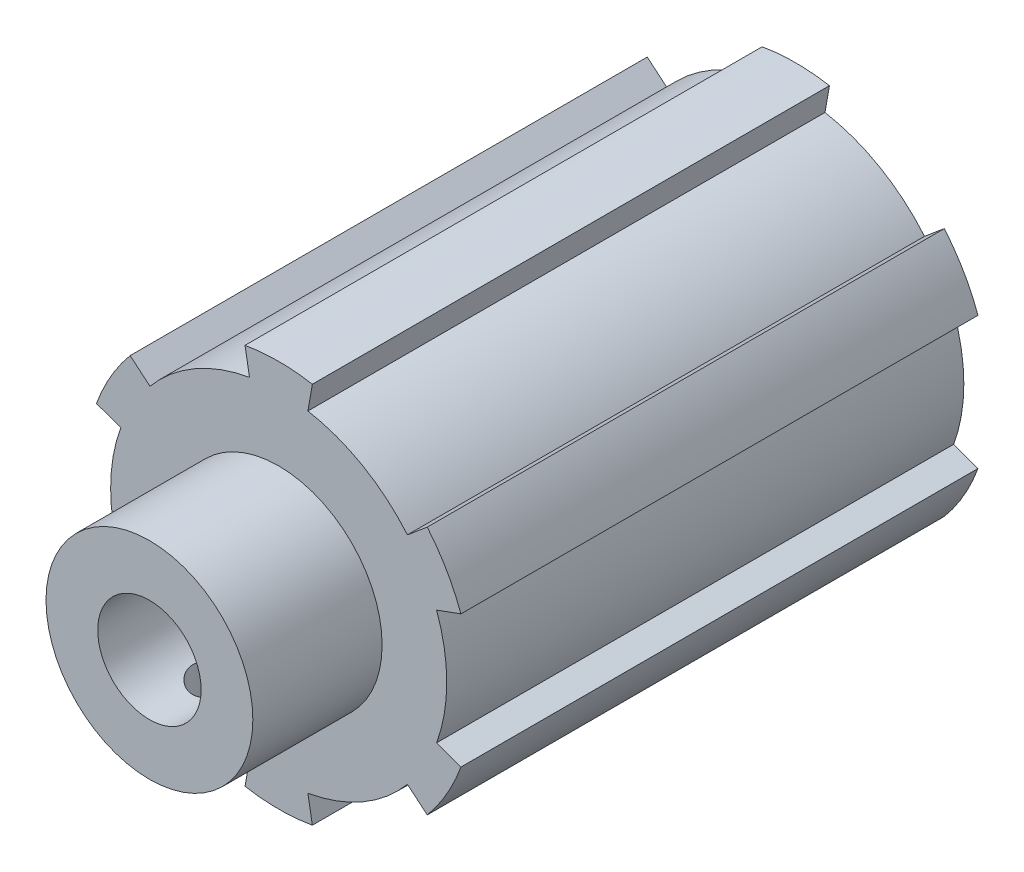
SolidWorks part; units mm, degrees
material "Silicon Rubber"
ref_plane "Plan de face" through (0, 0, 0) normal (0, 0, 1) x (1, 0, 0)
ref_plane "Plan de dessus" through (0, 0, 0) normal (0, 1, 0) x (1, 0, 0)
ref_plane "Plan de droite" through (0, 0, 0) normal (1, 0, 0) x (0, 0, -1)
sketch "Esquisse1" plane through (0, 0, 0) normal (0, 0, 1) x (1, 0, 0)
  circle A0 centre (0, 0) radius 60
  dimension "D1" = 120
extrude "Boss.-Extru.1" add sketch "Esquisse1" along normal blind 40
ref_axis "Axis1" through (0, 0, -2) along (0, 0, 1)
sketch "Sketch2" plane through (0, 0, 0) normal (0, 1, 0) x (1, 0, 0)
  line L0 (0, 0) -> (-57, 0)
  line L1 (60, 0) -> (-60, 0) construction
  line L2 (-57, 0) -> (0, -15)
  line L3 (0, -15) -> (0, 0)
  line L5 (-60, 0) -> (-60, -40) construction
  dimension "D2" = 15
  dimension "D3" = 3
sketch "Sketch3" plane through (0, 0, 0) normal (0, 0, 1) x (1, 0, 0)
  line L0 (0, 60) -> (0, -60) construction
  line L1 (-3.9433, 23.1806) -> (-7.5, 44.088)
  line L2 (7.5, 44.088) -> (3.9433, 23.1806)
  circle A0 centre (0, 0) radius 60 construction
  arc A1 (-2.8565, 49.9183) -> (2.8565, 49.9183) centre (0, 0) cw
  arc A2 (7.5, 44.088) -> (2.8565, 49.9183) centre (2.5708, 44.9265) ccw
  arc A3 (-7.5, 44.088) -> (-2.8565, 49.9183) centre (-2.5708, 44.9265) cw
  arc A4 (-3.9433, 23.1806) -> (3.9433, 23.1806) centre (0, 23.8514) ccw
  point P9 (0, 50)
  dimension "D1" = 10
  dimension "D2" = 5
  dimension "D3" = 4
  dimension "D4" = 15
extrude "Cut-Extrude4" cut sketch "Sketch3" against normal through all and the other way through all
pattern_circular "CirPattern1" count 10 over 360 about axis through (0, 0, -2) along (0, 0, 1) of "Cut-Extrude4"
sketch "Sketch4" plane through (0, 0, 40) normal (0, 0, 1) x (1, 0, 0)
  circle A0 centre (0, 0) radius 8
  dimension "D1" = 16
extrude "Boss-Extrude1" add sketch "Sketch4" along normal blind 10
sketch "Sketch5" plane through (0, 0, 50) normal (0, 0, 1) x (1, 0, 0)
  circle A0 centre (0, 0) radius 4
  dimension "D1" = 8
extrude "Cut-Extrude5" cut sketch "Sketch5" against normal through all
sketch "Sketch6" plane through (0, 0, 40) normal (0, 0, 1) x (1, 0, 0)
  line L0 (10.4189, 59.0885) -> (9.8979, 56.134)
  line L1 (14.7527, 55.0578) -> (15.5291, 57.9555)
  line L2 (0, 60) -> (0, 0) construction
  arc A0 (9.8979, 56.134) -> (14.7527, 55.0578) centre (0, 0) cw
  circle A1 centre (0, 0) radius 60
  arc A2 (15.5291, 57.9555) -> (10.4189, 59.0885) centre (0, 0) ccw
  circle A3 centre (0, 0) radius 60 construction
  dimension "D3" = 3
  dimension "D2" = 5
  dimension "D4" = 10
  dimension "D1" = 0
extrude "Cut-Extrude6" cut sketch "Sketch6" against normal blind 20 contours L1 A2 L0 A0 region at (12.6605, 57.1077, 40)
pattern_circular "CirPattern2" count 15 over 360 about axis through (0, 0, -2) along (0, 0, 1) of "Cut-Extrude6"
sketch "Sketch7" plane through (0, 0, 0) normal (0, 0, -1) x (-1, 0, 0)
  line L0 (-2.6172, 59.9429) -> (-2.4863, 56.9457)
  line L1 (2.4863, 56.9457) -> (2.6172, 59.9429)
  line L2 (0, 60) -> (0, 0) construction
  arc A0 (-2.4863, 56.9457) -> (2.4863, 56.9457) centre (0, 0) cw
  circle A1 centre (0, 0) radius 60 construction
  arc A6 (2.6172, 59.9429) -> (-2.6172, 59.9429) centre (0, 0) ccw
  point P6 (0, 60)
  dimension "D1" = 3
  dimension "D2" = 5
extrude "Cut-Extrude7" cut sketch "Sketch7" against normal blind 20
pattern_circular "CirPattern3" count 15 over 360 about axis through (0, 0, 15) along (0, 0, -1) of "Cut-Extrude7" reverse direction yes
sketch "Sketch8" plane through (0, 0, 40) normal (0, 0, 1) x (1, 0, 0)
  line L0 (-2.6047, 14.7721) -> (-2.2574, 12.8025)
  line L1 (2.6047, 14.7721) -> (2.2574, 12.8025)
  line L2 (0, 15) -> (0, 0) construction
  line L3 (11.4907, 9.6418) -> (9.9586, 8.3562)
  line L4 (14.0954, 5.1303) -> (12.216, 4.4463)
  line L5 (14.0954, -5.1303) -> (12.216, -4.4463)
  line L6 (11.4907, -9.6418) -> (9.9586, -8.3562)
  line L7 (2.6047, -14.7721) -> (2.2574, -12.8025)
  line L8 (-2.6047, -14.7721) -> (-2.2574, -12.8025)
  line L9 (-11.4907, -9.6418) -> (-9.9586, -8.3562)
  line L10 (-14.0954, -5.1303) -> (-12.216, -4.4463)
  line L12 (-14.0954, 5.1303) -> (-12.216, 4.4463)
  line L13 (-11.4907, 9.6418) -> (-9.9586, 8.3562)
  circle A3 centre (0, 0) radius 15 construction
  arc A7 (-12.216, 4.4463) -> (-12.216, -4.4463) centre (0, 0) ccw
  arc A10 (-2.6047, 14.7721) -> (2.6047, 14.7721) centre (0, 0) cw
  arc A11 (11.4907, 9.6418) -> (14.0954, 5.1303) centre (0, 0) cw
  arc A12 (14.0954, -5.1303) -> (11.4907, -9.6418) centre (0, 0) cw
  arc A13 (2.6047, -14.7721) -> (-2.6047, -14.7721) centre (0, 0) cw
  arc A14 (-11.4907, -9.6418) -> (-14.0954, -5.1303) centre (0, 0) cw
  arc A15 (-14.0954, 5.1303) -> (-11.4907, 9.6418) centre (0, 0) cw
  circle A17 centre (0, 0) radius 13 construction
  arc A18 (-9.9586, -8.3562) -> (-2.2574, -12.8025) centre (0, 0) ccw
  arc A19 (2.2574, -12.8025) -> (9.9586, -8.3562) centre (0, 0) ccw
  arc A20 (12.216, -4.4463) -> (12.216, 4.4463) centre (0, 0) ccw
  arc A21 (9.9586, 8.3562) -> (2.2574, 12.8025) centre (0, 0) ccw
  arc A22 (-2.2574, 12.8025) -> (-9.9586, 8.3562) centre (0, 0) ccw
  point P34 (0, 0)
  dimension "D1" = 30
  dimension "D2" = 2
  dimension "D3" = 20
  dimension "D4" = 6
extrude "Cut-Extrude8" cut sketch "Sketch8" against normal through all both and the other way through all flip side to cut
sketch "Sketch9" plane through (0, 0, 0) normal (0, 1, 0) x (1, 0, 0)
  line L0 (-8, -40) -> (-8, -50) construction
  line L1 (-8, -45) -> (8, -45) construction
  line L2 (8, -50) -> (8, -40) construction
  circle A0 centre (0, -45) radius 1.65
  point P4 (0, -45)
  point P11 (0, -45)
  dimension "D1" = 3.3
extrude "Cut-Extrude9" cut sketch "Sketch9" against normal up to next
